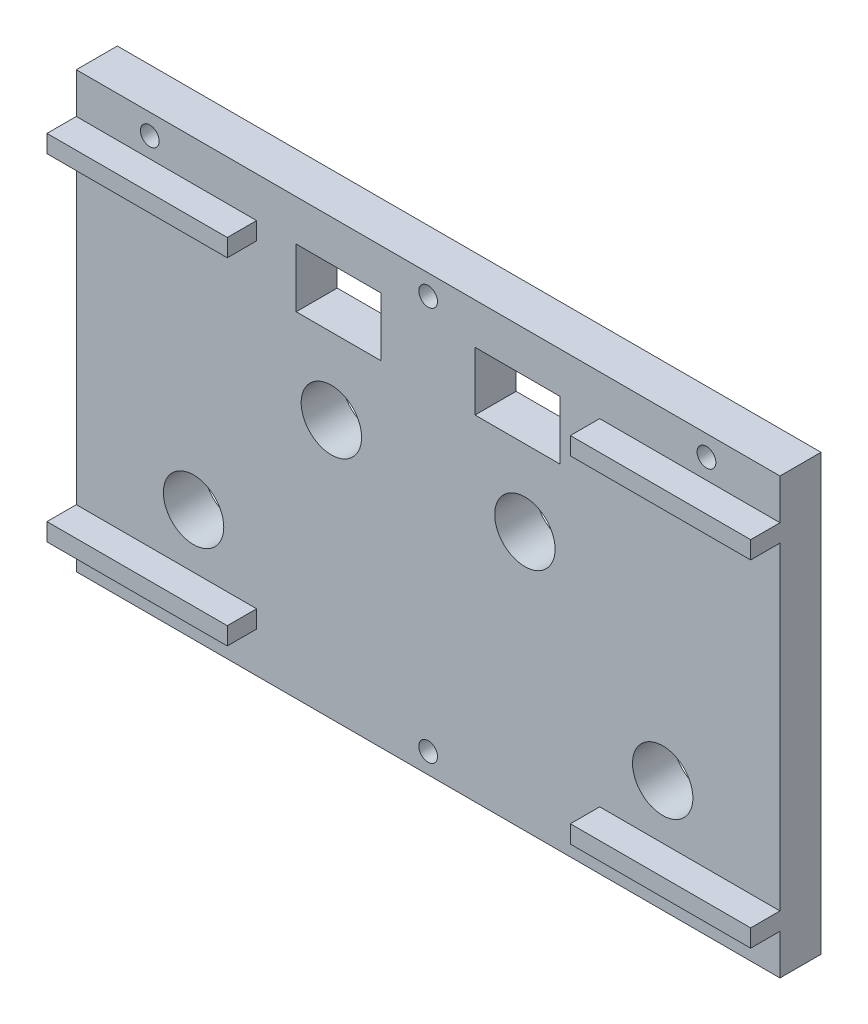
SolidWorks part; units mm, degrees
ref_plane "Plano frontal" through (0, 0, 0) normal (0, 0, 1) x (1, 0, 0)
ref_plane "Plano superior" through (0, 0, 0) normal (0, 1, 0) x (1, 0, 0)
ref_plane "Plano direito" through (0, 0, 0) normal (1, 0, 0) x (0, 0, -1)
sketch "Esboço1" plane through (0, 0, 0) normal (0, 0, 1) x (1, 0, 0)
  line L0 (-60, -0.0489) -> (60.0874, -0.0489) construction
  line L1 (-59.9126, 33.5488) -> (60.0874, 33.5488)
  line L4 (60.0874, 33.5488) -> (60.0874, -33.6467)
  line L5 (-59.9126, 33.5488) -> (60.0874, -33.6467) construction
  line L6 (-59.9126, -33.4512) -> (60.0874, 33.5488) construction
  line L7 (-39.9126, -26.5911) -> (-39.9126, -40.5911) construction
  line L8 (-11.2992, 33.5488) -> (-11.2992, 26.5488) construction
  line L9 (-59.9126, 26.644) -> (60.0874, 26.644) construction
  line L10 (-47.3753, 26.5589) -> (-47.3753, 3.5589) construction
  line L11 (60.0874, -33.6467) -> (60.0874, -40.5911)
  line L12 (-59.9126, 33.5488) -> (-59.9126, -33.4512)
  line L14 (-59.9126, -40.5911) -> (-59.9126, -33.4512)
  line L15 (-59.9126, -40.5911) -> (60.0874, -40.5911)
  line L16 (0.0874, 15.6099) -> (-29.9126, 15.6099) construction
  line L17 (0.0874, 26.6293) -> (0.0874, 33.5488) construction
  line L22 (-47.3753, 26.5589) -> (-47.3753, 33.5488) construction
  line L23 (-47.3753, 30.0538) -> (-59.9126, 30.0538) construction
  line L30 (0.0874, 21.2807) -> (-7.9126, 21.2807) construction
  line L32 (0.0874, 33.5488) -> (0.0874, -40.5911) construction
  line L35 (-7.9126, 21.2807) -> (-7.9126, 26.5488) construction
  line L38 (-7.9126, 26.5488) -> (-22.4126, 26.5488)
  line L39 (-7.9126, 26.5488) -> (-7.9126, 16.5488)
  line L40 (-7.9126, 16.5488) -> (-22.4126, 16.5488)
  line L44 (-16.4126, 26.5488) -> (-16.4126, -0.0489) construction
  line L45 (-47.3753, 3.5589) -> (-16.4126, 3.5589) construction
  line L46 (60.0874, 23.644) -> (29.3396, 23.644)
  line L47 (-59.9126, 26.644) -> (-29.1648, 26.644)
  line L48 (-59.9126, 26.644) -> (-59.9126, 23.644)
  line L49 (-59.9126, 23.644) -> (-29.1648, 23.644)
  line L50 (-29.1648, 26.644) -> (-29.1648, 23.644)
  line L51 (29.3396, 26.644) -> (29.3396, 23.644)
  line L52 (60.0874, 26.644) -> (29.3396, 26.644)
  line L53 (60.0874, 26.644) -> (60.0874, 23.644)
  line L54 (0.0874, -3.5212) -> (-59.9126, -3.5212) construction
  line L55 (-59.9126, -30.6863) -> (-29.1648, -30.6863)
  line L56 (-29.1648, -33.6863) -> (-29.1648, -30.6863)
  line L57 (-59.9126, -33.6863) -> (-29.1648, -33.6863)
  line L58 (-59.9126, -33.6863) -> (-59.9126, -30.6863)
  line L60 (60.0874, -33.6863) -> (29.3396, -33.6863)
  line L61 (-59.9126, -16.68) -> (60.0874, -16.68) construction
  line L69 (-16.4126, 3.5589) -> (-16.4126, -21.4411) construction
  line L70 (-16.4126, -21.4411) -> (-39.9126, -21.4411) construction
  line L71 (29.3396, -33.6863) -> (29.3396, -30.6863)
  line L72 (60.0874, -30.6863) -> (29.3396, -30.6863)
  line L73 (60.0874, -33.6863) -> (60.0874, -30.6863)
  line L74 (-7.9126, 21.2807) -> (-22.4126, 21.2807) construction
  line L75 (-22.4126, 26.5488) -> (-22.4126, 16.5488)
  line L76 (8.0874, 26.5488) -> (22.5874, 26.5488)
  line L77 (22.5874, 26.5488) -> (22.5874, 16.5488)
  line L78 (8.0874, 16.5488) -> (22.5874, 16.5488)
  line L79 (8.0874, 26.5488) -> (8.0874, 16.5488)
  circle A4 centre (0.0874, 30.0891) radius 1.6
  circle A5 centre (-47.3753, 30.0538) radius 1.6
  circle A6 centre (47.5501, 30.0538) radius 1.6
  circle A7 centre (-16.4126, 3.5589) radius 5.15
  circle A8 centre (16.5874, 3.5589) radius 5.15
  circle A17 centre (-39.9126, -21.4411) radius 5.15
  circle A18 centre (40.0874, -21.4411) radius 5.15
  circle A19 centre (47.5501, -37.0962) radius 1.6
  circle A20 centre (0.0874, -37.1314) radius 1.6
  circle A21 centre (-47.3753, -37.0962) radius 1.6
  circle A24 centre (40.0874, -21.4411) radius 5.15
  point P0 (0, 0)
  dimension "D6" = 10.3
  dimension "D9" = 12.5373
  dimension "D13" = 3.2
  dimension "D14" = 3.2
  dimension "D12" = 3
  dimension "D8" = 14
  dimension "D16" = 14.5
  dimension "D21" = 7
  dimension "D22" = 25
  dimension "D23" = 23.5
  dimension "D7" = 10.3
  dimension "D1" = 120
  dimension "D2" = 67
  dimension "D3" = 6.9445
  dimension "D4" = 7
  dimension "D5" = 23
  dimension "D10" = 30
  dimension "D11" = 8
  dimension "D15" = 10
  dimension "D17" = 14.5
extrude "Ressalto-extrusão1" add sketch "Esboço1" along normal blind 7 contours L72 L4 L46 L51 L52 L1 L12 L47 L50 L49 L55 L56 L57 L14 L15 L11 L60 L71 A20 A19 A8 A7 L75 L38 L39 L40 L79 L76 L77 L78 A4 A5 A6 A17 A18 A21 | L14 L57 L56 L55 L12 | L4 L72 L71 L60 L11 | L4 L52 L51 L46 | L50 L47 L12 L49
extrude "Ressalto-extrusão3" add sketch "Esboço1<5>" along normal blind 5 from surface contours L50 L47 L12 L49 | L4 L52 L51 L46 | L14 | L11 region at (-44.5387, 25.144, 0) region at (44.7135, 25.144, 0) region at (-44.5387, -32.1863, 0) region at (44.7135, -32.1863, 0) starting at face at (0.0874, -3.5212, 7)
sketch "Esboço1<5>" plane through (0, 0, 0) normal (0, 0, 1) x (1, 0, 0) same geometry as "Esboço1"
